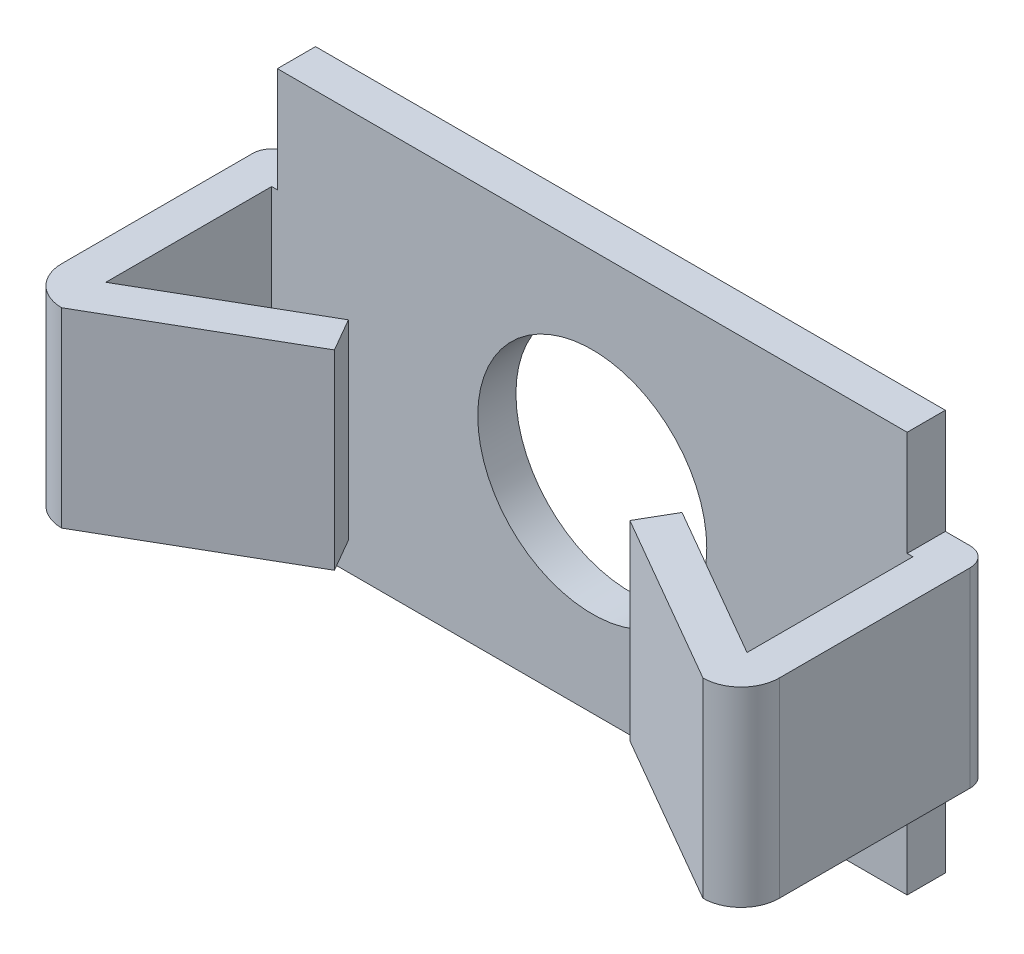
SolidWorks part; units mm, degrees
ref_plane "前视基准面" through (0, 0, 0) normal (0, 0, 1) x (1, 0, 0)
ref_plane "上视基准面" through (0, 0, 0) normal (0, 1, 0) x (1, 0, 0)
ref_plane "右视基准面" through (0, 0, 0) normal (1, 0, 0) x (0, 0, -1)
sketch "草图1" plane through (0, 0, 0) normal (0, 0, 1) x (1, 0, 0)
  line L1 (-18.8, -10.5) -> (18.8, -10.5)
  line L2 (-18.8, -10.5) -> (-18.8, 10.5)
  line L3 (-18.8, 10.5) -> (18.8, 10.5)
  line L4 (18.8, -10.5) -> (18.8, 10.5)
  line L5 (-18.8, -10.5) -> (18.8, 10.5) construction
  line L6 (-18.8, 10.5) -> (18.8, -10.5) construction
  point P0 (0, 0)
  dimension "D1" = 37.6
  dimension "D2" = 21
extrude "凸台-拉伸1" add sketch "草图1" along normal blind 2
sketch "草图2" plane through (0, 0, 2) normal (0, 0, 1) x (1, 0, 0)
  line L0 (0, 10.5) -> (0, -10.5) construction
  line L1 (18.8, 10.5) -> (-18.8, 10.5) construction
  line L2 (-18.8, -10.5) -> (18.8, -10.5) construction
  line L3 (-16.5, 10.5) -> (-16.5, 5)
  line L4 (16.5, 10.5) -> (16.5, 5)
  line L5 (-16.5, 0) -> (-18.8, 0) construction
  line L6 (-18.8, 10.5) -> (-18.8, -10.5) construction
  line L7 (16.5, 0) -> (18.8, 0) construction
  line L8 (18.8, -10.5) -> (18.8, 10.5) construction
  line L9 (-16.5, 5) -> (-18.8, 5)
  line L10 (-16.5, -5) -> (-18.8, -5)
  line L11 (16.5, 5) -> (18.8, 5)
  line L12 (16.5, -5) -> (18.8, -5)
  line L13 (-16.5, -5) -> (-16.5, -10.5)
  line L14 (16.5, -5) -> (16.5, -10.5)
  line L15 (-16.5, 10.5) -> (-16.5, -10.5) construction
  line L16 (-18.8, 5) -> (-18.8, 10.5)
  line L17 (16.5, 10.5) -> (16.5, -10.5) construction
  line L18 (-18.8, 10.5) -> (-16.5, 10.5)
  line L19 (-18.8, -5) -> (-18.8, -10.5)
  line L20 (-18.8, -10.5) -> (-16.5, -10.5)
  line L21 (16.5, 10.5) -> (18.8, 10.5)
  line L22 (18.8, 10.5) -> (18.8, 5)
  line L23 (16.5, -10.5) -> (18.8, -10.5)
  line L24 (18.8, -10.5) -> (18.8, -5)
  dimension "D1" = 16.5
  dimension "D2" = 16.5
  dimension "D3" = 5
  dimension "D4" = 5
  dimension "D5" = 5
  dimension "D6" = 5
extrude "切除-拉伸1" cut sketch "草图2" against normal through all
sketch "草图4" plane through (-18.8, 0, 0) normal (-1, 0, 0) x (0, 0, 1)
  line L0 (0, 5) -> (13, 5)
  line L1 (13, 5) -> (13, -5)
  line L2 (13, -5) -> (0, -5)
  line L3 (0, -5) -> (0, 5)
  dimension "D1" = 13
extrude "凸台-拉伸2" add sketch "草图4" against normal blind 2
sketch "草图5" plane through (0, 5, 0) normal (0, 1, 0) x (1, 0, 0)
  line L0 (-16.8, -13) -> (-16.8, -2) construction
  line L1 (-8.7404, -6.0374) -> (-16.8, -10.6906)
  line L2 (-7.7404, -7.7694) -> (-16.8, -13)
  line L3 (-16.8, -10.6906) -> (-16.8, -13)
  line L4 (-8.7404, -6.0374) -> (-7.7404, -7.7694)
  line L5 (-8.603, -5.958) -> (-19.2142, -12.0845) construction
  line L7 (-7.603, -7.6901) -> (-18.2142, -13.8165) construction
  dimension "D2" = 60
  dimension "D1" = 2
extrude "凸台-拉伸4" add sketch "草图5" against normal up to surface (10 mm away) up to face at (-17.3667, -5, 5)
sketch "草图6" plane through (0, 0, 0) normal (0, 0, -1) x (-1, 0, 0)
  circle A0 centre (0, 0) radius 6
  dimension "D1" = 12
extrude "切除-拉伸2" cut sketch "草图6" against normal through all
mirror "镜向2" about plane through (0, 0, 0) normal (1, 0, 0) of "凸台-拉伸2"
mirror "镜向3" about plane through (0, 0, 0) normal (1, 0, 0) of "凸台-拉伸4"
fillet "圆角1" radius 2 2 edges at (18.8, 0, 13) (-18.8, 0, 13)
fillet "圆角2" radius 1 2 edges at (18.8, 0, 0) (-18.8, 0, 0)
